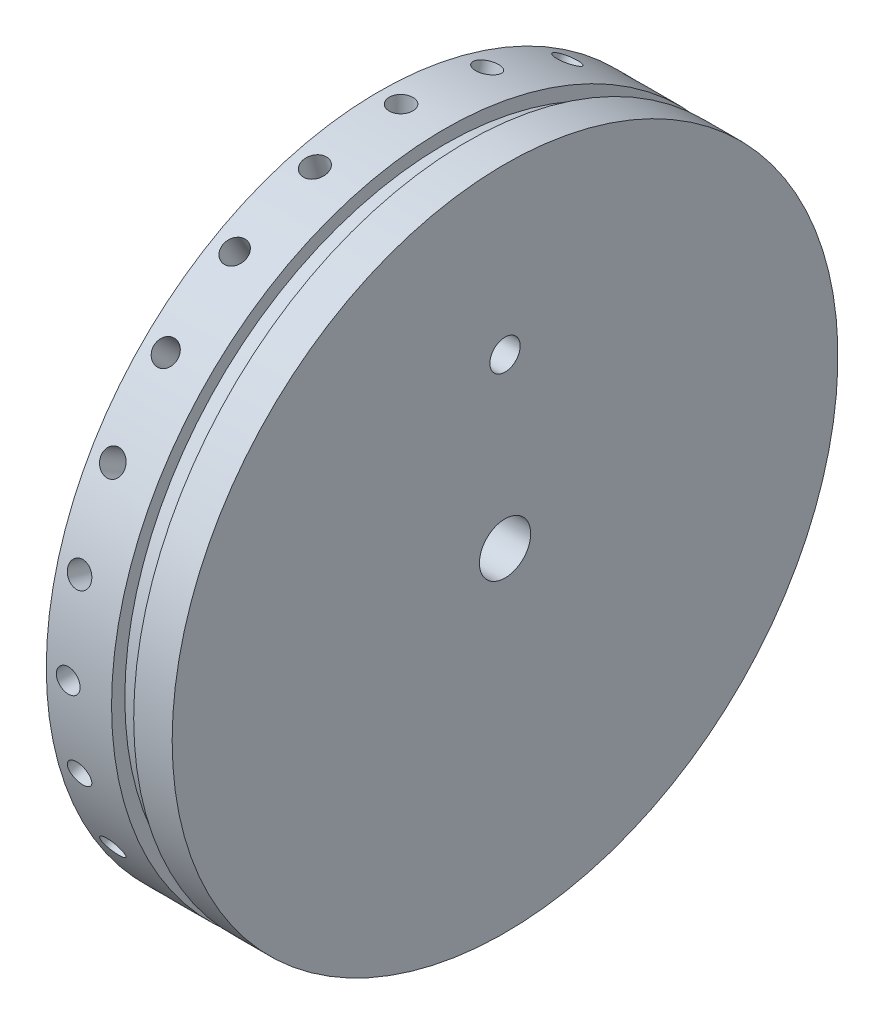
SolidWorks part; units mm, degrees
ref_plane "Front Plane" through (0, 0, 0) normal (0, 0, 1) x (1, 0, 0)
ref_plane "Top Plane" through (0, 0, 0) normal (0, 1, 0) x (1, 0, 0)
ref_plane "Right Plane" through (0, 0, 0) normal (1, 0, 0) x (0, 0, -1)
sketch "Cap Body Sketch" plane through (0, 0, 0) normal (0, 0, 1) x (1, 0, 0)
  line L0 (-1000, 0) -> (1000, 0) construction
  line L1 (8, 0) -> (8, 15.2)
  line L2 (8, 15.2) -> (13, 15.2)
  line L3 (13, 15.2) -> (13, 58)
  line L4 (13, 58) -> (8, 58)
  line L5 (8, 58) -> (8, 71.4)
  line L6 (8, 71.4) -> (22, 71.4)
  line L7 (22, 71.4) -> (22, 68.555)
  line L8 (22, 68.555) -> (26.75, 68.555)
  line L9 (26.75, 68.555) -> (26.75, 71.4)
  line L10 (26.75, 71.4) -> (35, 71.4)
  line L11 (35, 71.4) -> (35, 0)
  line L12 (35, 0) -> (8, 0)
revolve "Cap Body" add sketch "Cap Body Sketch" angle 360 about L0
ref_axis "Engine Axis" through (36.35, 0, 0) along (-1, 0, 0)
ref_plane "Boss Face" through (8, 0, 0) normal (1, 0, 0) x (0, 0, -1)
ref_plane "Port Face" through (13, 0, 0) normal (1, 0, 0) x (0, 0, -1)
sketch "Outlet Port Thread Bore Sketch" plane through (8, 0, 0) normal (1, 0, 0) x (0, 0, -1)
  circle A0 centre (0, 0) radius 8.73
extrude "Outlet Port Thread Bore" cut sketch "Outlet Port Thread Bore Sketch" along normal blind 14.3
ref_plane "Outlet Port Passage Plane" through (22.3, 0, 0) normal (1, 0, 0) x (0, 0, -1)
sketch "Outlet Port Passage Sketch" plane through (22.3, 0, 0) normal (1, 0, 0) x (0, 0, -1)
  circle A0 centre (0, 0) radius 5.5
extrude "Outlet Port Passage" cut sketch "Outlet Port Passage Sketch" along normal blind 12.7
sketch "Fill Port Thread Bore Sketch" plane through (13, 0, 0) normal (1, 0, 0) x (0, 0, -1)
  circle A0 centre (0, 36) radius 4.953
extrude "Fill Port Thread Bore" cut sketch "Fill Port Thread Bore Sketch" along normal blind 10.5
ref_plane "Fill Port Passage Plane" through (23.5, 0, 0) normal (1, 0, 0) x (0, 0, -1)
sketch "Fill Port Passage Sketch" plane through (23.5, 0, 0) normal (1, 0, 0) x (0, 0, -1)
  circle A0 centre (0, 36) radius 3.25
extrude "Fill Port Passage" cut sketch "Fill Port Passage Sketch" along normal blind 11.5
sketch "Screw Hole Sketch" plane through (0, 0, 0) normal (0, 0, 1) x (1, 0, 0)
  line L0 (12.7, 51.4) -> (12.7, 91.4) construction
  line L1 (12.7, 60.9) -> (15.25, 60.9)
  line L2 (15.25, 60.9) -> (15.25, 72.4)
  line L3 (15.25, 72.4) -> (12.7, 72.4)
  line L4 (12.7, 72.4) -> (12.7, 60.9)
revolve "Screw Hole" cut sketch "Screw Hole Sketch" angle 360 about L0
pattern_circular "Screw Holes x24" count 24 over 360 about axis through (36.35, 0, 0) along (-1, 0, 0) of "Screw Hole"
